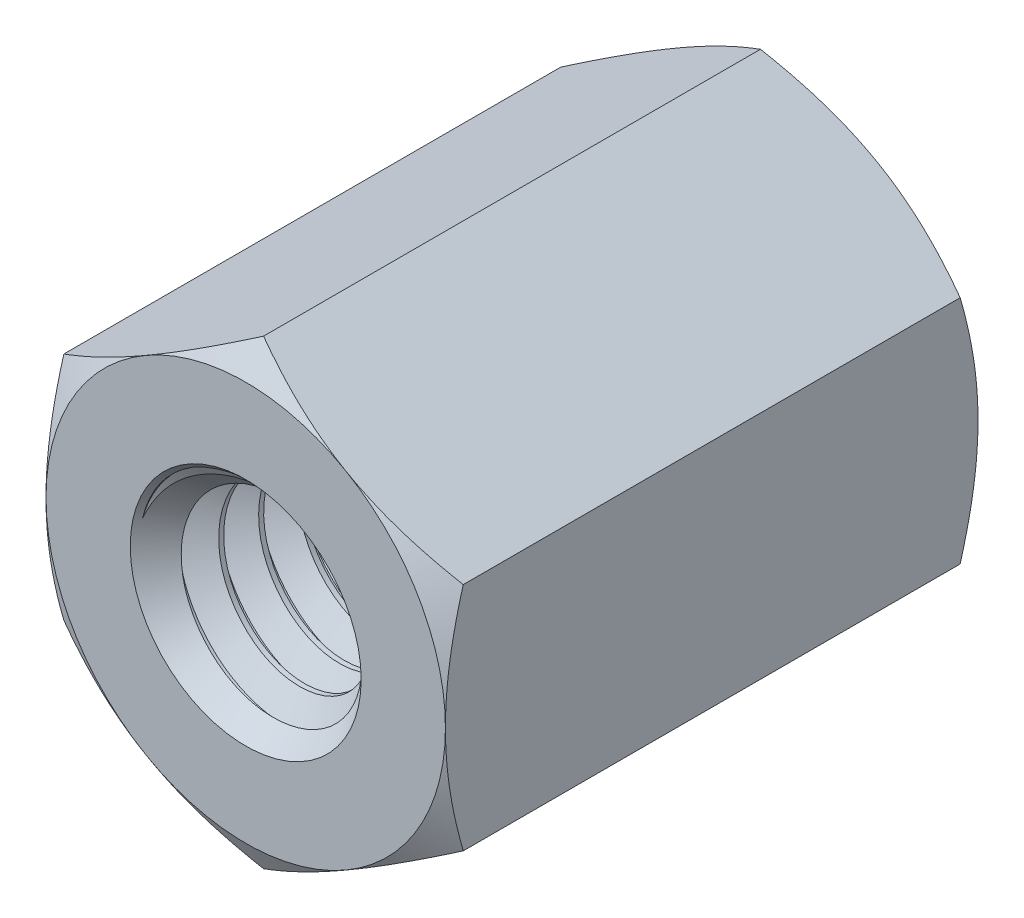
SolidWorks part; units mm, degrees
ref_plane "Front Plane" through (0, 0, 0) normal (0, 0, 1) x (1, 0, 0)
ref_plane "Top Plane" through (0, 0, 0) normal (0, 1, 0) x (1, 0, 0)
ref_plane "Right Plane" through (0, 0, 0) normal (1, 0, 0) x (0, 0, -1)
sketch "Sketch3" plane through (0, 0, 0) normal (1, 0, 0) x (0, 0, -1)
  line L0 (-3, 0) -> (3, 0) construction
  line L1 (0, 2.25) -> (0, -2.25) construction
  line L2 (-3, 1.25) -> (-3, -1.25) construction
  point P2 (-1.8, 0)
  point P3 (1.8, 0)
  dimension "Length" = 6
  dimension "Min Thread Length" = 4.8
  dimension "D1" = 4.8
  dimension "Thread Dia" = 2.5
  dimension "Hex" = 4.5
sketch "Sketch1" plane through (0, 0, 0) normal (0, 0, 1) x (1, 0, 0)
  line L1 (0, 2.5981) -> (-2.25, 1.299)
  line L2 (-2.25, 1.299) -> (-2.25, -1.299)
  line L3 (-2.25, -1.299) -> (0, -2.5981)
  line L4 (0, -2.5981) -> (2.25, -1.299)
  line L5 (2.25, -1.299) -> (2.25, 1.299)
  line L6 (2.25, 1.299) -> (0, 2.5981)
  circle A0 centre (0, 0) radius 2.25 construction
  circle A1 centre (0, 0) radius 1.25
extrude "Extrude1" add sketch "Sketch1" along normal up to vertex (3 mm away) and the other way up to vertex (3 mm away) up to point (0, 0, 3) other way up to point (0, 0, -3)
sketch "Sketch11" plane through (0, 0, -3) normal (0, 0, -1) x (-1, 0, 0)
  circle A0 centre (0, 0) radius 1.25 construction
  circle A1 centre (0, 0) radius 1.25
curve "Helix/Spiral1" pitch 0.45 height 6.45 radius 1.25 centre (0, 0, -3) axis (0, 0, 1) start towards (0, 1, 0) parameters "Pitch"=0.45
sketch "Sketch12" plane through (0, 0, 0) normal (1, 0, 0) x (0, 0, -1)
  line L0 (3.3938, 1.25) -> (3, 1.25)
  line L1 (3.3938, 1.25) -> (3.225, 0.9577)
  line L2 (3.225, 0.9577) -> (3.1688, 0.9577)
  line L3 (3.1688, 0.9577) -> (3, 1.25)
  line L4 (3.1969, 0.9577) -> (3.1969, 1.25) construction
  line L5 (3.3094, 1.1039) -> (3.0844, 1.1039) construction
  dimension "D1" = 0.0563
  dimension "D2" = 0.225
  dimension "D3" = 60
sweep "Sweep1" add profiles "Sketch12" path "Helix/Spiral1"
sketch "Sketch6" plane through (0, 0, -3) normal (0, 0, -1) x (-1, 0, 0)
  line L6 (0, 2.5981) -> (-2.25, 1.299)
  line L7 (-2.25, 1.299) -> (-2.25, -1.299)
  line L8 (-2.25, -1.299) -> (0, -2.5981)
  line L9 (0, -2.5981) -> (2.25, -1.299)
  line L10 (2.25, -1.299) -> (2.25, 1.299)
  line L11 (2.25, 1.299) -> (0, 2.5981)
  line L12 (0, 2.5981) -> (-2.25, 1.299)
  line L13 (-2.25, 1.299) -> (-2.25, -1.299)
  line L14 (-2.25, -1.299) -> (0, -2.5981)
  line L15 (0, -2.5981) -> (2.25, -1.299)
  line L16 (2.25, -1.299) -> (2.25, 1.299)
  line L17 (2.25, 1.299) -> (0, 2.5981)
  dimension "D1" = 0
extrude "Extrude2" cut sketch "Sketch6" along normal through all
sketch "Sketch7" plane through (0, 0, -3) normal (0, 0, -1) x (-1, 0, 0)
  circle A2 centre (0, 0) radius 1.3008
  circle A3 centre (0, 0) radius 1.3008
  dimension "D1" = 0.0508
extrude "Extrude3" cut sketch "Sketch7" against normal through all draft 43
sketch "Sketch8" plane through (0, 0, -3) normal (0, 0, -1) x (-1, 0, 0)
  circle A0 centre (0, 0) radius 2.25 construction
  circle A1 centre (0, 0) radius 2.25
extrude "Extrude4" cut sketch "Sketch8" against normal through all draft 60 flip side to cut
mirror "Mirror1" about plane through (0, 0, 0) normal (0, 0, 1) of "Extrude2", "Extrude3", "Extrude4"
sketch "Sketch9" [suppressed] plane through (0, 0, 0) normal (1, 0, 0) x (0, 0, -1)
  line L1 (-1.2, 1.1353) -> (1.2, 1.1353)
  line L2 (-1.2, 1.1353) -> (-1.2, 0)
  line L3 (-1.2, 0) -> (1.2, 0)
  line L4 (1.2, 1.1353) -> (1.2, 0)
  line L7 (-6, 0) -> (6, 0) construction
revolve "Revolve" [suppressed] add sketch "Sketch9" angle 360 about L0
sketch "Sketch10" [suppressed] plane through (0, 0, 0) normal (1, 0, 0) x (0, 0, -1)
  line L0 (6, 1.25) -> (1.2, 1.25)
  line L1 (-6, 1.25) -> (-1.2, 1.25)
  line L2 (1.2, 1.25) -> (1.2, -1.25)
  line L3 (-6, -1.25) -> (-1.2, -1.25)
  line L4 (-1.2, 1.25) -> (-1.2, -1.25)
  line L5 (1.2, -1.25) -> (6, -1.25)
ref_axis "Axis1" through (0, 0, -3.4666) along (0, 0, 1)
equation "\"D1@Sketch3\" = \"Min Thread Length@Sketch3\""
equation "\"D3@Helix/Spiral1\" = \"Length@Sketch3\"+\"Pitch@Helix/Spiral1\""
equation "\"D1@Sketch12\" = \"Pitch@Helix/Spiral1\"*.125"
equation "\"D2@Sketch12\" = \"Pitch@Helix/Spiral1\"*.5"
